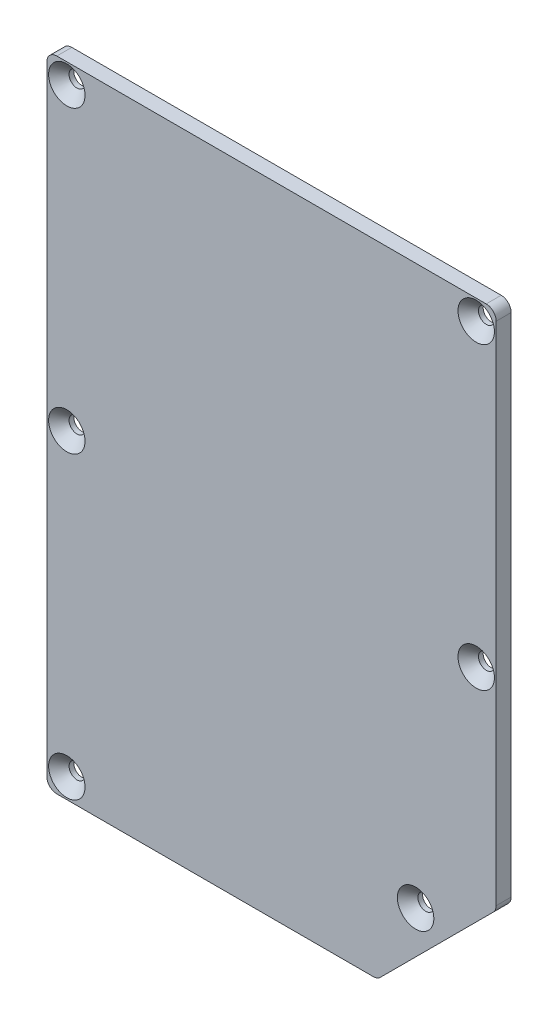
SolidWorks part; units mm, degrees
ref_plane "Front Plane" through (0, 0, 0) normal (0, 0, 1) x (1, 0, 0)
ref_plane "Top Plane" through (0, 0, 0) normal (0, 1, 0) x (1, 0, 0)
ref_plane "Right Plane" through (0, 0, 0) normal (1, 0, 0) x (0, 0, -1)
sketch "Sketch1" plane through (0, 0, 0) normal (0, 0, 1) x (1, 0, 0)
  line L5 (-45, 66) -> (-45, -58)
  line L6 (-43, -60) -> (20.3848, -60)
  line L7 (21.799, -59.4142) -> (44.4142, -36.799)
  line L8 (45, -35.3848) -> (45, 66)
  line L9 (43, 68) -> (-43, 68)
  line L10 (-45, 66) -> (-45, -58)
  line L11 (-43, -60) -> (20.3848, -60)
  line L12 (21.799, -59.4142) -> (44.4142, -36.799)
  line L13 (45, -35.3848) -> (45, 66)
  line L14 (43, 68) -> (-43, 68)
  arc A5 (-45, -58) -> (-43, -60) centre (-43, -58) ccw
  arc A6 (20.3848, -60) -> (21.799, -59.4142) centre (20.3848, -58) ccw
  arc A7 (44.4142, -36.799) -> (45, -35.3848) centre (43, -35.3848) ccw
  arc A8 (45, 66) -> (43, 68) centre (43, 66) ccw
  arc A9 (-43, 68) -> (-45, 66) centre (-43, 66) ccw
  arc A10 (-45, -58) -> (-43, -60) centre (-43, -58) ccw
  arc A11 (20.3848, -60) -> (21.799, -59.4142) centre (20.3848, -58) ccw
  arc A12 (44.4142, -36.799) -> (45, -35.3848) centre (43, -35.3848) ccw
  arc A13 (45, 66) -> (43, 68) centre (43, 66) ccw
  arc A14 (-43, 68) -> (-45, 66) centre (-43, 66) ccw
  dimension "D1" = 0
extrude "Boss-Extrude1" add sketch "Sketch1" along normal blind 3
sketch "Sketch5" plane through (0, 0, 3) normal (0, 0, 1) x (1, 0, 0)
  point P0 (-41, 64)
  point P1 (41, 64)
  point P3 (41, 4)
  point P5 (28.864, -43.864)
  point P7 (-41, -56)
  point P9 (-41, 4)
  point P11 (-41, 64)
hole_wizard "CSK for M3 Countersunk Flat Head Screw1" positions "3DSketch3" profile "Sketch6" countersink size "M3" standard "ISO"
sketch3d "3DSketch3"
  point P0 (-41, -56, 3)
  point P3 (28.864, -43.864, 3)
  point P6 (41, 4, 3)
  point P9 (-41, 4, 3)
  point P12 (-41, 64, 3)
  point P15 (41, 64, 3)
sketch "Sketch6" plane through (-41, -56, 3) normal (1, 0, 0) x (0, -1, 0)
  line L0 (0, 0) -> (0, 5.9614)
  line L1 (0, 5.9614) -> (1.6, 5)
  line L2 (1.6, 5) -> (1.6, 2.05)
  line L3 (1.6, 2.05) -> (3.65, 0)
  line L5 (3.65, 0) -> (0, 0)
  line L6 (-1.6, 2.05) -> (-3.65, 0) construction
  line L10 (0, 5.9614) -> (-1.6, 5) construction
  line L11 (0, -6.35) -> (0, 107.95) construction
  dimension "Hole Dia." = 3.2
  dimension "Hole Depth" = 5
  dimension "Near C'Sink Dia." = 7.3
  dimension "Near C'Sink Angle" = 90
  dimension "Drill Angle" = 118
